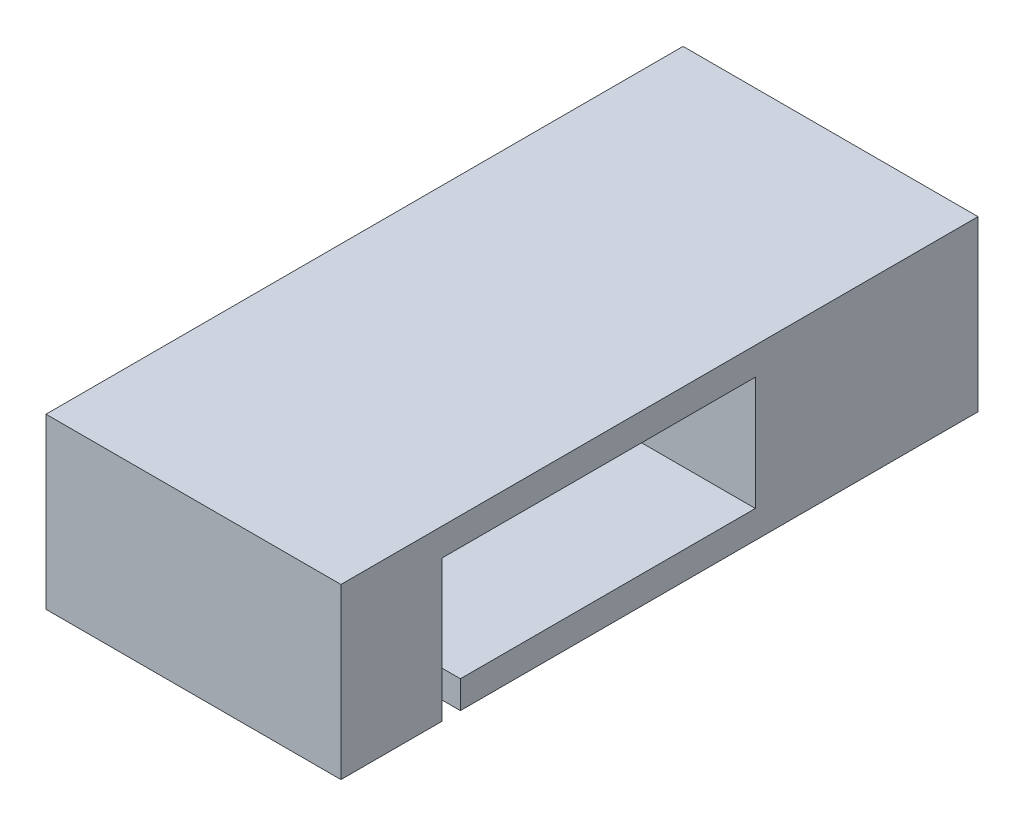
SolidWorks part; units mm, degrees
ref_plane "Front Plane" through (0, 0, 0) normal (0, 0, 1) x (1, 0, 0)
ref_plane "Top Plane" through (0, 0, 0) normal (0, 1, 0) x (1, 0, 0)
ref_plane "Right Plane" through (0, 0, 0) normal (1, 0, 0) x (0, 0, -1)
sketch "Sketch2" plane through (0, 0, 0) normal (0, 1, 0) x (1, 0, 0)
  line L1 (-16, -34.56) -> (16, -34.56)
  line L2 (-16, -34.56) -> (-16, 34.56)
  line L3 (-16, 34.56) -> (16, 34.56)
  line L4 (16, -34.56) -> (16, 34.56)
  line L5 (-16, -34.56) -> (16, 34.56) construction
  line L6 (-16, 34.56) -> (16, -34.56) construction
  point P0 (0, 0)
  dimension "D1" = 32
  dimension "D2" = 69.12
extrude "Boss-Extrude1" add sketch "Sketch2" along normal blind 18.34
sketch "Sketch3" plane through (16, 0, 0) normal (1, 0, 0) x (0, 0, -1)
  line L0 (-34.56, 18.34) -> (34.56, 18.34) construction
  line L1 (-23.6, 15.34) -> (10.4, 15.34)
  line L2 (-23.6, 15.34) -> (-23.6, 3)
  line L4 (10.4, 15.34) -> (10.4, 3)
  line L5 (-23.6, 15.34) -> (10.4, 3) construction
  line L6 (-23.6, 3) -> (10.4, 15.34) construction
  line L7 (-34.56, 0) -> (34.56, 0) construction
  line L8 (-23.6, 3) -> (-23.6, 0)
  line L9 (-23.6, 0) -> (-21.6, 0)
  line L10 (-21.6, 0) -> (-21.6, 3)
  line L11 (-21.6, 3) -> (10.4, 3)
  circle A0 centre (0, 9.17) radius 2.305 construction
  point P2 (-6.6, 9.17)
  point P12 (-23.6, 9.17)
  point P18 (10.4, 9.17)
  dimension "D1" = 3
  dimension "D5" = 4.61
  dimension "D2" = 32
  dimension "D3" = 34
  dimension "D4" = 10.4
  dimension "D6" = 2
  dimension "D7" = 3
extrude "Cut-Extrude1" cut sketch "Sketch3" against normal blind 29
sketch "Sketch4" plane through (-16, 0, 0) normal (-1, 0, 0) x (0, 0, 1)
  circle A0 centre (0, 9.17) radius 2.305
  point P3 (0, 0)
  dimension "D1" = 4.61
extrude "Boss-Extrude3" add sketch "Sketch4" along normal blind 6
